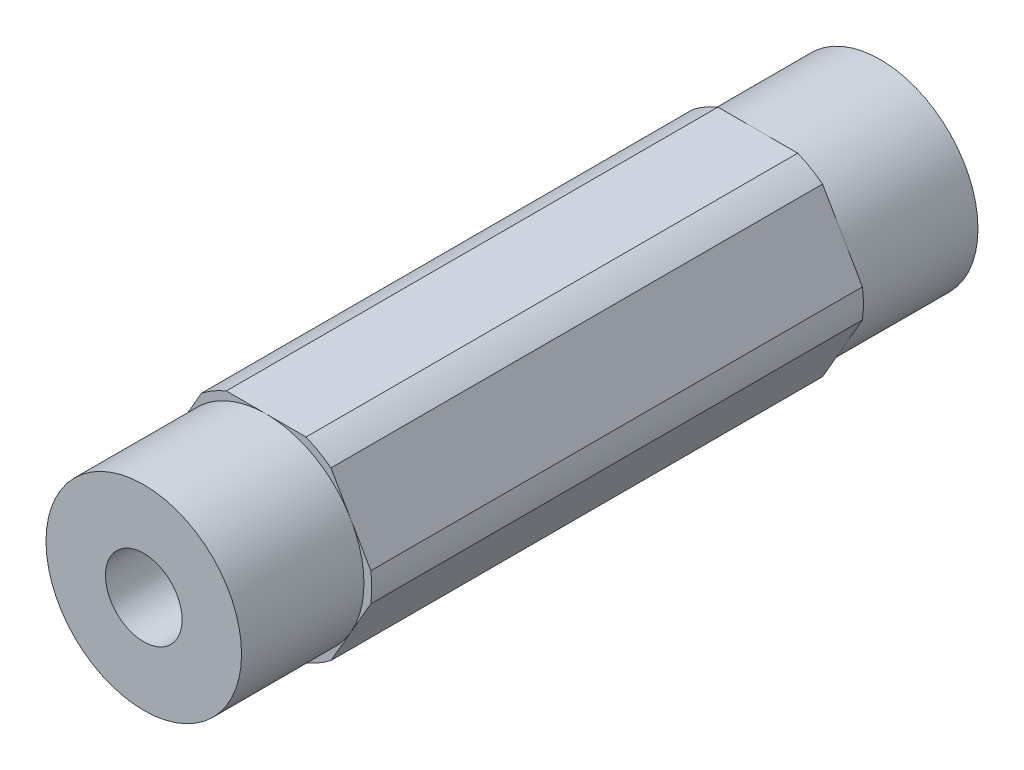
SolidWorks part; units mm, degrees
ref_plane "Front Plane" through (0, 0, 0) normal (0, 0, 1) x (1, 0, 0)
ref_plane "Top Plane" through (0, 0, 0) normal (0, 1, 0) x (1, 0, 0)
ref_plane "Right Plane" through (0, 0, 0) normal (1, 0, 0) x (0, 0, -1)
sketch "Sketch1" plane through (0, 0, 0) normal (0, 0, 1) x (1, 0, 0)
  line L1 (7.3323, 0) -> (3.6662, 6.35)
  line L2 (3.6662, 6.35) -> (-3.6662, 6.35)
  line L3 (-3.6662, 6.35) -> (-7.3323, 0)
  line L4 (-7.3323, 0) -> (-3.6662, -6.35)
  line L5 (-3.6662, -6.35) -> (3.6662, -6.35)
  line L6 (3.6662, -6.35) -> (7.3323, 0)
  circle A0 centre (0, 0) radius 6.35 construction
  dimension "D1" = 12.7
extrude "Boss-Extrude1" add sketch "Sketch1" along normal mid plane 47.8282
sketch "Sketch3" plane through (0, 0, 23.9141) normal (0, 0, 1) x (1, 0, 0)
  circle A0 centre (0, 0) radius 6.35
extrude "Cut-Extrude2" cut sketch "Sketch3" against normal blind 7.9502 flip side to cut
sketch "Sketch4" plane through (0, 0, 23.9141) normal (0, 0, 1) x (1, 0, 0)
  circle A0 centre (0, 0) radius 6.858
  dimension "D1" = 13.716
extrude "Cut-Extrude3" cut sketch "Sketch4" against normal through all flip side to cut
sketch "Sketch5" plane through (0, 0, 23.9141) normal (0, 0, 1) x (1, 0, 0)
  circle A0 centre (0, 0) radius 2.4892
  dimension "D1" = 4.9784
extrude "Cut-Extrude4" cut sketch "Sketch5" against normal through all
mirror "Mirror1" about plane through (0, 0, 0) normal (0, 0, 1) of "Cut-Extrude2"
equation "\"D1@Boss-Extrude1\"=1.87300+0.01"
